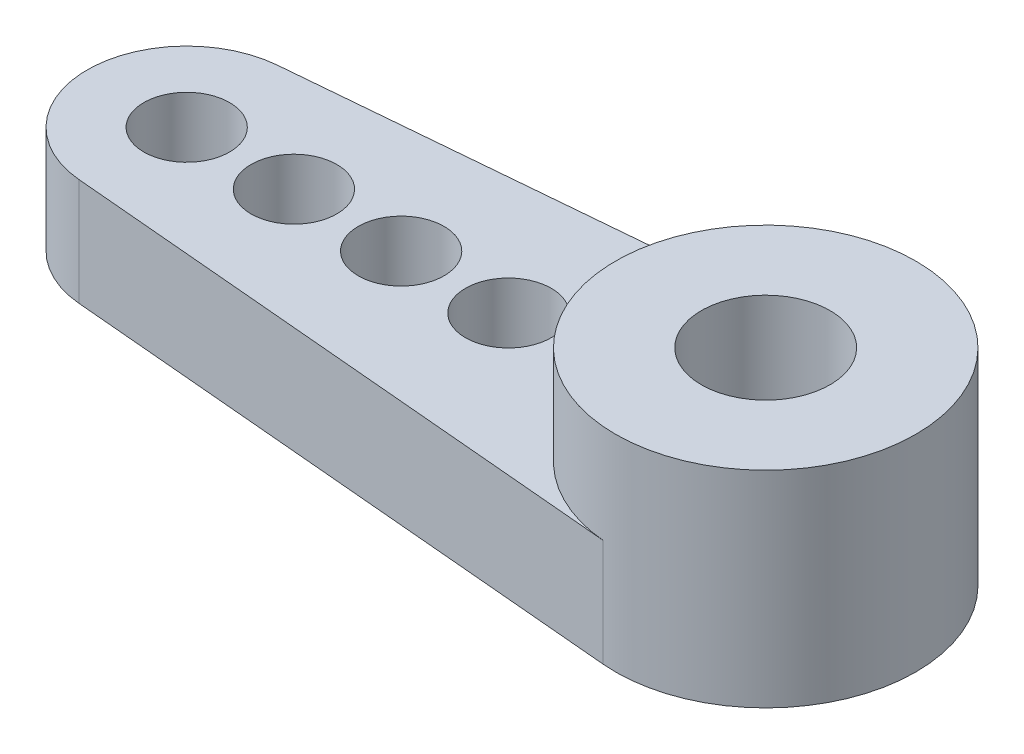
SolidWorks part; units mm, degrees
material "7075-O (SS)"
ref_plane "前视基准面" through (0, 0, 0) normal (0, 0, 1) x (1, 0, 0)
ref_plane "上视基准面" through (0, 0, 0) normal (0, 1, 0) x (1, 0, 0)
ref_plane "右视基准面" through (0, 0, 0) normal (1, 0, 0) x (0, 0, -1)
other "Configuration Table"
sketch "草图1" plane through (0, 0, 0) normal (0, 1, 0) x (1, 0, 0)
  line L0 (-0.3059, 3.4866) -> (-13.7028, 2.3111)
  line L1 (-0.3059, -3.4866) -> (-13.7028, -2.3111)
  line L2 (3.5, 0) -> (-15.82, 0) construction
  circle A0 centre (0, 0) radius 1.5
  circle A1 centre (0, 0) radius 3.5
  circle A2 centre (-6, 0) radius 1
  circle A3 centre (-8.5, 0) radius 1
  circle A4 centre (-11, 0) radius 1
  circle A5 centre (-13.5, 0) radius 1
  circle A6 centre (-13.5, 0) radius 2.32 construction
  arc A7 (-13.7028, 2.3111) -> (-13.7028, -2.3111) centre (-13.5, 0) ccw
  arc A8 (-0.3059, -3.4866) -> (-0.3059, 3.4866) centre (0, 0) ccw
  point P19 (-11, 0)
  point P20 (-8.5, 0)
  point P21 (-6, 0)
  point P22 (-13.6119, 0)
  dimension "D6" = 2
  dimension "D8" = 3
  dimension "D1" = 6
  dimension "D2" = 8.5
  dimension "D3" = 11
  dimension "D4" = 13.5
  dimension "D5" = 19.32
  dimension "D7" = 2.32
extrude "凸台-拉伸1" add sketch "草图1" along normal blind 2.5 contours L0 A7 L1 A1 A2 A3 A4 A5 region at (-3.6701, 0, 0)
extrude "凸台-拉伸2" add sketch "草图1<3>" along normal blind 4.8 contours A1 A0 region at (2.2974, 0, -2.5078)
sketch "草图1<3>" plane through (0, 0, 0) normal (0, 1, 0) x (1, 0, 0) same geometry as "草图1"
